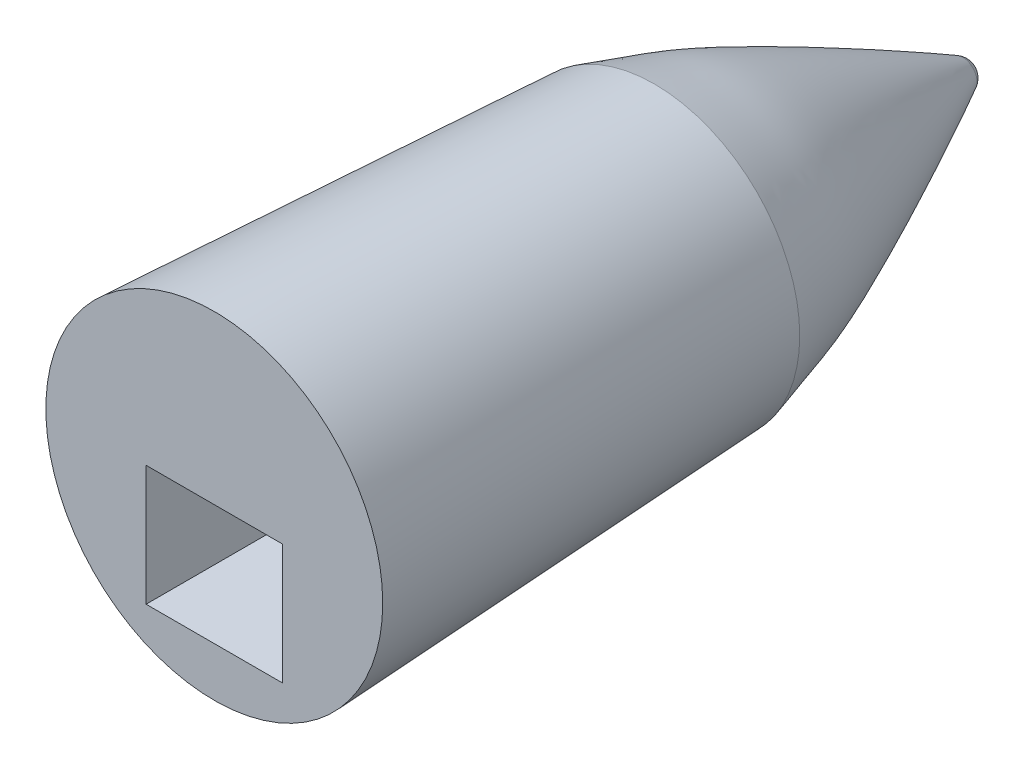
SolidWorks part; units mm, degrees
material "Свинец без примесей"
ref_plane "Спереди" through (0, 0, 0) normal (0, 0, 1) x (1, 0, 0)
ref_plane "Сверху" through (0, 0, 0) normal (0, 1, 0) x (1, 0, 0)
ref_plane "Справа" through (0, 0, 0) normal (1, 0, 0) x (0, 0, -1)
sketch "Эскиз1" plane through (0, 0, 0) normal (0, 1, 0) x (1, 0, 0)
  line L0 (0, 0) -> (0, 80) construction
  line L1 (0, 0) -> (-25, 0) construction
  line L2 (-21, 2) -> (-21, -18) construction
  line L5 (-21, -20) -> (0, -20)
  line L8 (-25, 0) -> (0, 80) construction
  line L10 (-21, 23.3035) -> (-21, -20)
  line L11 (0, 76.5095) -> (0, -20)
  line L12 (-2, -18) -> (-2, 66.8948) construction
  line L13 (-21, -18) -> (-2, -18) construction
  line L14 (0, -20) -> (0, 80) construction
  line L15 (-22.2796, 2) -> (-2, 66.8948) construction
  line L16 (-21.7437, -20) -> (0, -20) construction
  line L20 (-21, -18) -> (0, -18) construction
  line L21 (-21.7437, -20) -> (-23, -20) construction
  line L22 (-22.2796, 2) -> (-21, 2) construction
  line L23 (-23.0191, 2) -> (-21, 2) construction
  line L24 (-21, -18) -> (-21, -18) construction
  line L25 (-21, -18) -> (-21, -18) construction
  line L26 (-23, 0) -> (-23, -20) construction
  line L27 (-21, 2) -> (-21, -18) construction
  line L28 (-25, 0) -> (-23, 0) construction
  spline S0 degree 3 poles (-25, 0) (-25.3345, 19.1075) (-20.4075, 33.8926) (-15.3337, 51.5733) (-1.1082, 79.7902) (0, 80) knots 0 0 0 0 0.501806 0.601806 1 1 1 1 construction
  spline S1 degree 1 poles (-23.0191, 2) (1.1823, 78.3869) knots 0 0 1 1 construction
  spline S2 degree 3 poles (-23.0191, 2) (-23.0199, 2.538) (-23.0142, 3.6222) (-22.9746, 5.7238) (-22.8747, 8.2734) (-22.6809, 11.1999) (-22.3338, 14.9367) (-21.7512, 19.309) (-20.8698, 24.1215) (-19.8618, 28.543) (-18.781, 32.6183) (-17.6838, 36.3877) (-16.7941, 39.3248) (-16.14, 41.546) (-15.6355, 43.1976) (-15.0242, 45.0124) (-13.9372, 47.8862) (-11.955, 52.5312) (-8.9966, 58.9452) (-6.3405, 64.4155) (-4.2832, 68.5097) (-2.819, 71.3511) (-1.4799, 73.8732) (-0.5075, 75.6326) (0.1572, 76.7835) (0.5917, 77.5048) (0.8871, 77.967) (1.0813, 78.2501) (1.1449, 78.3375) (1.1823, 78.3869) knots 0.017702 0.017702 0.017702 0.017702 0.032587 0.047472 0.077243 0.107013 0.136783 0.196324 0.255865 0.315406 0.374947 0.434488 0.494029 0.523799 0.553569 0.58334 0.61311 0.672651 0.732192 0.791733 0.821503 0.851274 0.881044 0.910815 0.9257 0.940585 0.95547 0.962913 0.970355 0.970355 0.970355 0.970355 only from (-21, 23.3035) to (0, 76.5095)
  dimension "D1" = 25
  dimension "D2" = 21
  dimension "D4" = 2
  dimension "D5" = 100
revolve "Повернуть1" add sketch "Эскиз1" angle 360 about L11
sketch "Эскиз2" plane through (0, 0, 0) normal (0, 1, 0) x (1, 0, 0)
  line L0 (21, -20) -> (21, 66.972)
  line L1 (21, -20) -> (16.442, 66.972)
  line L2 (21, 66.972) -> (16.442, 66.972)
  dimension "D1" = 3
ref_axis "Ось1" through (0, 0, 20) along (0, 0, -1)
revolve "Вырез-Повернуть1" cut sketch "Эскиз2" angle 360 about axis through (0, 0, 20) along (0, 0, -1)
sketch "Эскиз3" plane through (0, 0, 0) normal (0, 1, 0) x (1, 0, 0)
  line L0 (0, 76.5095) -> (0, 74.3882)
  line L5 (1.7622, 73.3341) -> (4.0259, 73.3341)
  line L7 (4.0259, 73.3341) -> (4.0259, 76.5095)
  line L8 (4.0259, 76.5095) -> (0, 76.5095)
  arc A2 (1.7622, 73.3341) -> (0, 74.3882) centre (0, 72.3882) ccw
revolve "Вырез-Повернуть2" cut sketch "Эскиз3" angle 360 about L0
sketch "Эскиз4" plane through (0, 0, 20) normal (0, 0, 1) x (1, 0, 0)
  line L1 (8.5, 0.1365) -> (-8.5, 0.1365)
  line L2 (8.5, 0.1365) -> (8.5, -14.8635)
  line L3 (8.5, -14.8635) -> (-8.5, -14.8635)
  line L4 (-8.5, 0.1365) -> (-8.5, -14.8635)
  line L5 (8.5, 0.1365) -> (-8.5, -14.8635) construction
  line L6 (8.5, -14.8635) -> (-8.5, 0.1365) construction
  point P0 (0, -7.3635)
  point P5 (0, 0)
  dimension "D1" = 15
  dimension "D2" = 17
extrude "Вырез-Вытянуть1" cut sketch "Эскиз4" against normal blind 30 contours L2 L1 L4 L3
sketch "Эскиз5" plane through (0, -14.8635, 0) normal (0, 1, 0) x (1, 0, 0)
  line L1 (8.5, 10) -> (-8.5, 10)
  line L2 (8.5, 10) -> (8.5, -2)
  line L3 (8.5, -2) -> (-8.5, -2)
  line L4 (-8.5, 10) -> (-8.5, -2)
  line L5 (-8.5, 10) -> (-8.5, -20) construction
  dimension "D1" = 12
  dimension "D2" = 0
extrude "Вырез-Вытянуть2" cut sketch "Эскиз5" along normal blind 25
